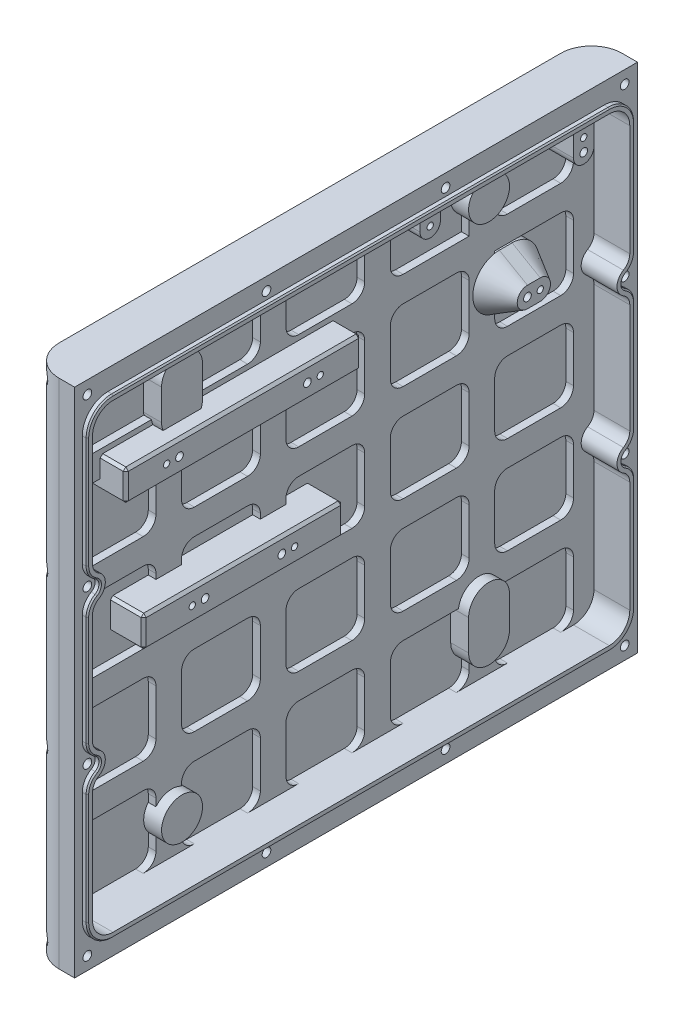
SolidWorks part; units mm, degrees
material "6061 Alloy"
ref_plane "Front Plane" through (0, 0, 0) normal (0, 0, 1) x (1, 0, 0)
ref_plane "Top Plane" through (0, 0, 0) normal (0, 1, 0) x (1, 0, 0)
ref_plane "Right Plane" through (0, 0, 0) normal (1, 0, 0) x (0, 0, -1)
sketch "Sketch1" plane through (0, 0, 0) normal (1, 0, 0) x (0, 0, -1)
  line L0 (-105, 25) -> (-105, -25)
  line L1 (-110, 100) -> (110, 100)
  line L2 (-110, 100) -> (-110, -100)
  line L3 (-110, -100) -> (110, -100)
  line L4 (110, 100) -> (110, -100)
  line L5 (-105, -35) -> (-105, -90)
  line L6 (105, 25) -> (105, -25)
  line L7 (-105, 90) -> (105, 90)
  line L8 (-105, 90) -> (-105, 35)
  line L9 (-105, -90) -> (105, -90)
  line L10 (105, 90) -> (105, 35)
  line L11 (105, -35) -> (105, -90)
  arc A0 (-105, 25) -> (-105, 35) centre (-105, 30) ccw
  arc A1 (-105, -35) -> (-105, -25) centre (-105, -30) ccw
  arc A2 (105, 35) -> (105, 25) centre (105, 30) ccw
  arc A3 (105, -25) -> (105, -35) centre (105, -30) ccw
  point P0 (0, 0)
  point P6 (0, 0)
  dimension "D10" = 60
  dimension "D11" = 10
  dimension "D1" = 220
  dimension "D2" = 200
  dimension "D3" = 210
  dimension "D4" = 180
  dimension "D5" = 90
  dimension "D6" = 100
  dimension "D7" = 105
  dimension "D8" = 110
  dimension "D9" = 60
extrude "Boss-Extrude1" add sketch "Sketch1" along normal blind 6 contours L2 L3 L4 L1
extrude "Boss-Extrude2" add sketch "Sketch1<3>" along normal blind 18
sketch "Sketch1<3>" plane through (0, 0, 0) normal (1, 0, 0) x (0, 0, -1) same geometry as "Sketch1"
sketch "Sketch2" plane through (6, 0, 0) normal (1, 0, 0) x (0, 0, -1)
  line L0 (90, 84) -> (90, 79) construction
  line L1 (94, 90) -> (94, 79)
  line L2 (86, 90) -> (86, 79)
  line L3 (68, 41) -> (73, 41) construction
  line L6 (105, 90) -> (-105, 90) construction
  line L7 (105, 35) -> (105, 90) construction
  line L8 (68, 45) -> (73, 45)
  line L9 (68, 37) -> (73, 37)
  line L10 (26, 84) -> (26, 90)
  line L11 (34, 84) -> (34, 90)
  line L12 (105, 90) -> (-105, 90) construction
  line L13 (34, 90) -> (26, 90)
  line L15 (86, 90) -> (94, 90)
  arc A1 (86, 79) -> (94, 79) centre (90, 79) ccw
  arc A2 (26, 84) -> (34, 84) centre (30, 84) ccw
  arc A5 (68, 45) -> (68, 37) centre (68, 41) ccw
  arc A6 (73, 37) -> (73, 45) centre (73, 41) ccw
  point P2 (90, 81.5)
  point P3 (0, 0)
  point P11 (70.5, 41)
  line M15 (105, 90) -> (-105, 90)
  dimension "D4" = 4
  dimension "D6" = 8
  dimension "D10" = 4
  dimension "D1" = 6
  dimension "D2" = 60
  dimension "D3" = 5
  dimension "D5" = 15
  dimension "D7" = 43
  dimension "D8" = 17
  dimension "D9" = 5
  dimension "D11" = 8
extrude "Boss-Extrude3" add sketch "Sketch2" along normal blind 11 contours L2 A1 L1 M15 | A2 L11 L13 L10 region at (6, 82.901, -90)
extrude "Boss-Extrude7" add sketch "Sketch2<3>" against normal blind 11 draft 30 from offset 11 contours A6 L8 A5 L9 draft outward yes
sketch "Sketch2<3>" plane through (6, 0, 0) normal (1, 0, 0) x (0, 0, -1) same geometry as "Sketch2"
sketch "Sketch3" plane through (17, 0, 0) normal (1, 0, 0) x (0, 0, -1)
  line L0 (94, 79) -> (94, 90) construction
  circle A0 centre (30, 84) radius 1.2295
  circle A1 centre (90, 84) radius 1.2295
  circle A2 centre (73, 41) radius 1.2295
  arc A3 (73, 37) -> (73, 45) centre (73, 41) ccw construction
  point P9 (0, 0)
  point P10 (0, 0)
  dimension "D1" = 2.459
  dimension "D2" = 4
extrude "Cut-Extrude1" cut sketch "Sketch3" against normal blind 7
hole_wizard "Ø3.0mm Dowel Hole1" positions "Sketch4" profile "Sketch5" hole size "Ø3.0" standard "ANSI Metric"
sketch "Sketch4" plane through (17, 0, 0) normal (1, 0, 0) x (0, 0, -1)
  arc A0 (68, 45) -> (68, 37) centre (68, 41) ccw construction
  point P0 (68, 41)
  point P3 (90, 79)
  point P6 (0, 0)
sketch "Sketch5" plane through (17, 41, -68) normal (0, 1, 0) x (0, 0, -1)
  line L0 (0, 0) -> (0, 5.9013)
  line L1 (0, 5.9013) -> (1.5, 5)
  line L2 (1.5, 5) -> (1.5, 0)
  line L5 (1.5, 0) -> (0, 0)
  line L10 (0, 5.9013) -> (-1.5, 5) construction
  line L11 (0, -6.35) -> (0, 107.95) construction
  dimension "Hole Dia." = 3
  dimension "Hole Depth" = 5
  dimension "Drill Angle" = 118
sketch "Sketch6" plane through (6, 0, 0) normal (1, 0, 0) x (0, 0, -1)
  line L0 (-42, 84.1007) -> (-42, -37.9382) construction
  line L1 (-88, 60) -> (4, 60)
  line L2 (-88, 60) -> (-88, 48)
  line L3 (-88, 48) -> (4, 48)
  line L4 (4, 60) -> (4, 48)
  line L5 (-81, 7) -> (-3, 7)
  line L6 (-81, 7) -> (-81, -5)
  line L7 (-81, -5) -> (-3, -5)
  line L8 (-3, 7) -> (-3, -5)
  line L9 (-105, 90) -> (-105, 35) construction
  line L10 (105, 90) -> (94, 90) construction
  dimension "D1" = 63
  dimension "D2" = 12
  dimension "D3" = 12
  dimension "D4" = 30
  dimension "D5" = 41
  dimension "D6" = 78
  dimension "D7" = 92
extrude "Boss-Extrude4" add sketch "Sketch6" along normal blind 10
sketch "Sketch7" plane through (16, 0, 0) normal (1, 0, 0) x (0, 0, -1)
  line L0 (-42, 60) -> (-42, -5) construction
  line L1 (4, 60) -> (-88, 60) construction
  line L2 (-81, -5) -> (-3, -5) construction
  line L3 (-3, 7) -> (-81, 7) construction
  circle A0 centre (-72, 54) radius 1.2295
  circle A1 centre (-12, 54) radius 1.2295
  circle A2 centre (-62, 1) radius 1.2295
  circle A3 centre (-22, 1) radius 1.2295
  dimension "D1" = 30
  dimension "D2" = 2.459
  dimension "D7" = 6
  dimension "D3" = 30
  dimension "D4" = 6
  dimension "D5" = 20
  dimension "D6" = 20
extrude "Cut-Extrude2" cut sketch "Sketch7" against normal blind 7
hole_wizard "Ø3.0mm Dowel Hole2" positions "Sketch9" profile "Sketch10" hole size "Ø3.0" standard "ANSI Metric"
sketch "Sketch9" plane through (16, 0, 0) normal (1, 0, 0) x (0, 0, -1)
  line L0 (4, 60) -> (-88, 60) construction
  line L1 (-3, 7) -> (-81, 7) construction
  circle A0 centre (-72, 54) radius 1.2295 construction
  circle A1 centre (-12, 54) radius 1.2295 construction
  circle A2 centre (-62, 1) radius 1.2295 construction
  circle A3 centre (-22, 1) radius 1.2295 construction
  point P0 (-67, 54)
  point P2 (-17, 54)
  point P4 (-57, 1)
  point P6 (-27, 1)
  dimension "D2" = 5
  dimension "D4" = 5
  dimension "D1" = 6
  dimension "D3" = 5
  dimension "D5" = 5
  dimension "D6" = 6
sketch "Sketch10" plane through (16, 54, 67) normal (0, 1, 0) x (0, 0, -1)
  line L0 (0, 0) -> (0, 4.9013)
  line L1 (0, 4.9013) -> (1.5, 4)
  line L2 (1.5, 4) -> (1.5, 0)
  line L5 (1.5, 0) -> (0, 0)
  line L10 (0, 4.9013) -> (-1.5, 4) construction
  line L11 (0, -6.35) -> (0, 107.95) construction
  dimension "Hole Dia." = 3
  dimension "Hole Depth" = 4
  dimension "Drill Angle" = 118
fillet "Fillet1" radius 8 4 edges at (12, -90, 105) (12, 90, 105) (12, -90, -105) (12, 90, -105)
fillet "Fillet2" radius 5 8 edges at (12, -25, -105) (12, -35, -105) (12, 25, -105) (12, 35, -105) (12, -35, 105) (12, -25, 105) (12, 25, 105) (12, 35, 105)
sketch "Sketch11" plane through (18, 0, 0) normal (1, 0, 0) x (0, 0, -1)
  line L0 (107, -82) -> (107, -38.6603)
  line L1 (-97, -92) -> (97, -92)
  line L2 (-107, -38.6603) -> (-107, -82)
  line L3 (-107, 21.3397) -> (-107, -21.3397)
  line L4 (-107, 82) -> (-107, 38.6603)
  line L5 (97, 92) -> (-97, 92)
  line L6 (107, 38.6603) -> (107, 82)
  line L7 (107, -21.3397) -> (107, 21.3397)
  line L8 (105, -21.3397) -> (105, 21.3397)
  line L9 (105, 38.6603) -> (105, 82)
  line L10 (97, 90) -> (94, 90)
  line L11 (-105, 82) -> (-105, 38.6603)
  line L12 (-105, 21.3397) -> (-105, -21.3397)
  line L13 (-105, -38.6603) -> (-105, -82)
  line L14 (-97, -90) -> (97, -90)
  line L15 (105, -82) -> (105, -38.6603)
  line L16 (105, -21.3397) -> (105, 21.3397)
  line L17 (105, 38.6603) -> (105, 82)
  line L18 (97, 90) -> (94, 90)
  line L19 (-105, 82) -> (-105, 38.6603)
  line L20 (-105, 21.3397) -> (-105, -21.3397)
  line L21 (-105, -38.6603) -> (-105, -82)
  line L22 (-97, -90) -> (97, -90)
  line L23 (105, -82) -> (105, -38.6603)
  line L38 (94, 90) -> (94, 79)
  line L40 (86, 79) -> (86, 90)
  line L42 (86, 90) -> (34, 90)
  line L44 (34, 90) -> (34, 84)
  line L46 (26, 84) -> (26, 90)
  line L48 (26, 90) -> (-97, 90)
  line L49 (94, 90) -> (-97, 90)
  arc A0 (103.5, -27.4019) -> (103.5, -32.5981) centre (105, -30) ccw
  arc A1 (107, -38.6603) -> (103.5, -32.5981) centre (100, -38.6603) ccw
  arc A2 (97, -92) -> (107, -82) centre (97, -82) ccw
  arc A3 (-107, -82) -> (-97, -92) centre (-97, -82) ccw
  arc A4 (-103.5, -32.5981) -> (-107, -38.6603) centre (-100, -38.6603) ccw
  arc A5 (-103.5, -32.5981) -> (-103.5, -27.4019) centre (-105, -30) ccw
  arc A6 (-107, -21.3397) -> (-103.5, -27.4019) centre (-100, -21.3397) ccw
  arc A7 (-103.5, 27.4019) -> (-107, 21.3397) centre (-100, 21.3397) ccw
  arc A8 (-103.5, 27.4019) -> (-103.5, 32.5981) centre (-105, 30) ccw
  arc A9 (-107, 38.6603) -> (-103.5, 32.5981) centre (-100, 38.6603) ccw
  arc A10 (-97, 92) -> (-107, 82) centre (-97, 82) ccw
  arc A11 (107, 82) -> (97, 92) centre (97, 82) ccw
  arc A12 (103.5, 32.5981) -> (107, 38.6603) centre (100, 38.6603) ccw
  arc A13 (103.5, 32.5981) -> (103.5, 27.4019) centre (105, 30) ccw
  arc A14 (107, 21.3397) -> (103.5, 27.4019) centre (100, 21.3397) ccw
  arc A15 (103.5, -27.4019) -> (107, -21.3397) centre (100, -21.3397) ccw
  arc A16 (102.5, -25.6699) -> (102.5, -34.3301) centre (105, -30) ccw
  arc A17 (102.5, -25.6699) -> (105, -21.3397) centre (100, -21.3397) ccw
  arc A18 (105, 21.3397) -> (102.5, 25.6699) centre (100, 21.3397) ccw
  arc A19 (102.5, 34.3301) -> (102.5, 25.6699) centre (105, 30) ccw
  arc A20 (102.5, 34.3301) -> (105, 38.6603) centre (100, 38.6603) ccw
  arc A21 (105, 82) -> (97, 90) centre (97, 82) ccw
  arc A22 (-97, 90) -> (-105, 82) centre (-97, 82) ccw
  arc A23 (-105, 38.6603) -> (-102.5, 34.3301) centre (-100, 38.6603) ccw
  arc A24 (-102.5, 25.6699) -> (-102.5, 34.3301) centre (-105, 30) ccw
  arc A25 (-102.5, 25.6699) -> (-105, 21.3397) centre (-100, 21.3397) ccw
  arc A26 (-105, -21.3397) -> (-102.5, -25.6699) centre (-100, -21.3397) ccw
  arc A27 (-102.5, -34.3301) -> (-102.5, -25.6699) centre (-105, -30) ccw
  arc A28 (-102.5, -34.3301) -> (-105, -38.6603) centre (-100, -38.6603) ccw
  arc A29 (-105, -82) -> (-97, -90) centre (-97, -82) ccw
  arc A30 (97, -90) -> (105, -82) centre (97, -82) ccw
  arc A31 (105, -38.6603) -> (102.5, -34.3301) centre (100, -38.6603) ccw
  arc A32 (102.5, -25.6699) -> (102.5, -34.3301) centre (105, -30) ccw
  arc A33 (102.5, -25.6699) -> (105, -21.3397) centre (100, -21.3397) ccw
  arc A34 (105, 21.3397) -> (102.5, 25.6699) centre (100, 21.3397) ccw
  arc A35 (102.5, 34.3301) -> (102.5, 25.6699) centre (105, 30) ccw
  arc A36 (102.5, 34.3301) -> (105, 38.6603) centre (100, 38.6603) ccw
  arc A37 (105, 82) -> (97, 90) centre (97, 82) ccw
  arc A38 (-97, 90) -> (-105, 82) centre (-97, 82) ccw
  arc A39 (-105, 38.6603) -> (-102.5, 34.3301) centre (-100, 38.6603) ccw
  arc A40 (-102.5, 25.6699) -> (-102.5, 34.3301) centre (-105, 30) ccw
  arc A41 (-102.5, 25.6699) -> (-105, 21.3397) centre (-100, 21.3397) ccw
  arc A42 (-105, -21.3397) -> (-102.5, -25.6699) centre (-100, -21.3397) ccw
  arc A43 (-102.5, -34.3301) -> (-102.5, -25.6699) centre (-105, -30) ccw
  arc A44 (-102.5, -34.3301) -> (-105, -38.6603) centre (-100, -38.6603) ccw
  arc A45 (-105, -82) -> (-97, -90) centre (-97, -82) ccw
  arc A46 (97, -90) -> (105, -82) centre (97, -82) ccw
  arc A47 (105, -38.6603) -> (102.5, -34.3301) centre (100, -38.6603) ccw
  arc A66 (86, 79) -> (94, 79) centre (90, 79) ccw
  arc A68 (26, 84) -> (34, 84) centre (30, 84) ccw
  dimension "D1" = 0
  dimension "D2" = 2
extrude "Boss-Extrude5" add sketch "Sketch11" along normal blind 2
chamfer "Chamfer1" distance 0.5 angle 45 24 edges at (20, -60.3301, -107) (20, -35.1603, -106.0622) (20, -89.0711, -104.0711) (20, -30, -102) (20, -92, 0) (20, -24.8397, -106.0622) (20, -89.0711, 104.0711) (20, 0, -107) (20, -60.3301, 107) (20, 24.8397, -106.0622) (20, -35.1603, 106.0622) (20, 30, -102) (20, -30, 102) (20, 35.1603, -106.0622) (20, -24.8397, 106.0622) (20, 60.3301, -107) (20, 0, 107) (20, 89.0711, -104.0711) (20, 24.8397, 106.0622) (20, 92, 0) (20, 30, 102) (20, 89.0711, 104.0711) (20, 35.1603, 106.0622) (20, 60.3301, 107)
sketch "Sketch12" plane through (18, 0, 0) normal (1, 0, 0) x (0, 0, -1)
  line L0 (110, 100) -> (-110, 100) construction
  line L2 (-110, -100) -> (110, -100) construction
  circle A0 centre (-105, 95) radius 1.7
  circle A1 centre (-105, 30) radius 1.7
  circle A2 centre (-105, -30) radius 1.7
  circle A3 centre (-105, -95) radius 1.7
  circle A4 centre (-35, -95) radius 1.7
  circle A5 centre (35, -95) radius 1.7
  circle A6 centre (105, -95) radius 1.7
  circle A7 centre (105, -30) radius 1.7
  circle A8 centre (105, 30) radius 1.7
  circle A9 centre (105, 95) radius 1.7
  circle A10 centre (-35, 95) radius 1.7
  circle A11 centre (35, 95) radius 1.7
  dimension "D2" = 3.4
  dimension "D3" = 5
  dimension "D1" = 5
  dimension "D4" = 70
  dimension "D5" = 70
extrude "Cut-Extrude3" cut sketch "Sketch12" against normal up to surface (18 mm away) up to face at (0, 0, 0)
sketch "Sketch13" plane through (0, 0, 0) normal (-1, 0, 0) x (0, 0, 1)
  circle A0 centre (-105, 95) radius 3.25
  circle A1 centre (-35, 95) radius 3.25
  circle A2 centre (35, 95) radius 3.25
  circle A3 centre (105, 95) radius 3.25
  circle A4 centre (105, 30) radius 3.25
  circle A5 centre (105, -30) radius 3.25
  circle A6 centre (105, -95) radius 3.25
  circle A7 centre (35, -95) radius 3.25
  circle A8 centre (-35, -95) radius 3.25
  circle A9 centre (-105, -95) radius 3.25
  circle A10 centre (-105, -30) radius 3.25
  circle A11 centre (-105, 30) radius 3.25
  dimension "D1" = 6.5
extrude "Cut-Extrude4" cut sketch "Sketch13" against normal blind 12
fillet "Fillet3" radius 12 2 edges at (0, 0, -110) (0, 0, 110)
sketch "Sketch14" plane through (0, 0, 0) normal (-1, 0, 0) x (0, 0, 1)
  line L0 (60, 75) -> (60, 63) construction
  line L1 (68, 75) -> (68, 63)
  line L2 (52, 75) -> (52, 63)
  line L3 (-60, -75) -> (-60, -63) construction
  line L4 (-68, -75) -> (-68, -63)
  line L5 (-52, -75) -> (-52, -63)
  circle A0 centre (-60, 75) radius 8
  circle A1 centre (60, -75) radius 8
  arc A2 (68, 75) -> (52, 75) centre (60, 75) ccw
  arc A3 (52, 63) -> (68, 63) centre (60, 63) ccw
  arc A4 (-68, -75) -> (-52, -75) centre (-60, -75) ccw
  arc A5 (-52, -63) -> (-68, -63) centre (-60, -63) ccw
  circle A6 centre (-60, -75) radius 2.4585
  circle A7 centre (60, -75) radius 2.4585
  circle A8 centre (-60, 75) radius 2.4585
  circle A9 centre (60, 75) radius 2.4585
  circle A10 centre (60, 63) radius 1.5
  circle A11 centre (-60, -63) radius 1.5
  point P6 (60, 69)
  point P12 (-60, -69)
  dimension "D5" = 16
  dimension "D6" = 8
  dimension "D7" = 12
  dimension "D8" = 4.917
  dimension "D9" = 3
  dimension "D1" = 120
  dimension "D2" = 150
  dimension "D3" = 75
  dimension "D4" = 60
extrude "Boss-Extrude6" add sketch "Sketch14" along normal blind 2 and the other way blind 10 contours A0 | L1 A3 L2 A2 | A1 | L5 A5 L4 A4
extrude "Cut-Extrude6" cut sketch "Sketch14<3>" against normal blind 6 from surface contours A10 | A9 | A8 | A7 | A6 | A11 starting at face at (-2, 69, 60)
sketch "Sketch14<3>" plane through (0, 0, 0) normal (-1, 0, 0) x (0, 0, 1) same geometry as "Sketch14"
sketch "Sketch15" plane through (6, 0, 0) normal (1, 0, 0) x (0, 0, -1)
  line L0 (-97, 90) -> (-97, 62)
  line L1 (97, 90) -> (97, 62)
  line L2 (-66.2, 90) -> (-66.2, 80.0557)
  line L3 (-56.2, 90) -> (-56.2, 82.0399)
  line L4 (-25.4, 90) -> (-25.4, 62)
  line L5 (-15.4, 90) -> (-15.4, 62)
  line L6 (15.4, 90) -> (15.4, 62)
  line L7 (25.4, 90) -> (25.4, 62)
  line L8 (56.2, 90) -> (56.2, 82.0399)
  line L9 (66.2, 90) -> (66.2, 80.0557)
  line L10 (-97, 62) -> (-67.9373, 62)
  line L11 (-97, 52) -> (-88, 52)
  line L12 (-97, 24) -> (-66.2, 24)
  line L13 (-97, 14) -> (-66.2, 14)
  line L14 (105, -21.3397) -> (105, 21.3397)
  line L15 (105, 38.6603) -> (105, 82)
  line L16 (97, 90) -> (94, 90)
  line L17 (94, 90) -> (94, 79)
  line L18 (86, 79) -> (86, 90)
  line L19 (86, 90) -> (34, 90)
  line L20 (34, 90) -> (34, 84)
  line L21 (26, 84) -> (26, 90)
  line L22 (26, 90) -> (-97, 90)
  line L23 (-105, 82) -> (-105, 38.6603)
  line L24 (-105, 21.3397) -> (-105, -21.3397)
  line L25 (-105, -38.6603) -> (-105, -82)
  line L26 (-97, -90) -> (97, -90)
  line L27 (105, -82) -> (105, -38.6603)
  line L30 (97, 90) -> (94, 90)
  line L31 (94, 90) -> (94, 79)
  line L32 (86, 79) -> (86, 90)
  line L33 (86, 90) -> (66.2, 90)
  line L34 (34, 90) -> (34, 84)
  line L35 (26, 84) -> (26, 90)
  line L36 (26, 90) -> (25.4, 90)
  line L40 (-97, -90) -> (-66.2, -90)
  line L42 (-97, -14) -> (-66.2, -14)
  line L43 (-97, -24) -> (-66.2, -24)
  line L44 (-97, -52) -> (-66.2, -52)
  line L45 (-97, -62) -> (-66.2, -62)
  line L46 (-66.2, 90) -> (-97, 90)
  line L47 (-97, -62) -> (-97, -90)
  line L48 (-66.2, -62) -> (-66.2, -69.9443)
  line L49 (-56.2, -62) -> (-56.2, -67.9601)
  line L50 (-56.2, -52) -> (-25.4, -52)
  line L51 (-56.2, -62) -> (-25.4, -62)
  line L52 (-66.2, -80.0557) -> (-66.2, -90)
  line L53 (-56.2, -82.0399) -> (-56.2, -90)
  line L54 (-25.4, -62) -> (-25.4, -90)
  line L55 (-15.4, -62) -> (-15.4, -90)
  line L56 (-15.4, -52) -> (15.4, -52)
  line L57 (-15.4, -62) -> (15.4, -62)
  line L58 (-56.2, -90) -> (-25.4, -90)
  line L59 (-15.4, -90) -> (15.4, -90)
  line L60 (-97, -24) -> (-97, -52)
  line L61 (-66.2, -24) -> (-66.2, -52)
  line L62 (-56.2, -24) -> (-56.2, -52)
  line L63 (-56.2, -14) -> (-25.4, -14)
  line L64 (-56.2, -24) -> (-25.4, -24)
  line L65 (-66.2, -5) -> (-66.2, -14)
  line L66 (-56.2, 14) -> (-56.2, 7)
  line L67 (-66.2, 14) -> (-66.2, 7)
  line L68 (-56.2, 24) -> (-25.4, 24)
  line L69 (-81, 7) -> (-81, -5)
  line L70 (-81, -5) -> (-3, -5)
  line L71 (-3, -5) -> (-3, 7)
  line L72 (-3, 7) -> (-81, 7)
  line L73 (-81, 7) -> (-81, -5)
  line L74 (-81, -5) -> (-66.2, -5)
  line L75 (-3, -5) -> (-3, 7)
  line L76 (-3, 7) -> (-15.4, 7)
  line L77 (-56.2, 14) -> (-25.4, 14)
  line L78 (-97, 14) -> (-97, -14)
  line L79 (-66.2, 7) -> (-81, 7)
  line L80 (-56.2, -5) -> (-25.4, -5)
  line L81 (-56.2, -5) -> (-56.2, -14)
  line L82 (-15.4, 24) -> (15.4, 24)
  line L83 (-15.4, 14) -> (15.4, 14)
  line L84 (-25.4, 14) -> (-25.4, 7)
  line L85 (-15.4, 14) -> (-15.4, 7)
  line L86 (-25.4, 7) -> (-56.2, 7)
  line L87 (-15.4, -5) -> (-3, -5)
  line L88 (-15.4, -14) -> (15.4, -14)
  line L89 (-25.4, -5) -> (-25.4, -14)
  line L90 (-25.4, -24) -> (-25.4, -52)
  line L91 (-15.4, -24) -> (-15.4, -52)
  line L92 (-15.4, -24) -> (15.4, -24)
  line L93 (25.4, -52) -> (56.2, -52)
  line L94 (25.4, -62) -> (52.0627, -62)
  line L95 (4, 48) -> (4, 60) construction
  line L96 (15.4, -62) -> (15.4, -90)
  line L98 (-52, 63) -> (-52, 75) construction
  line L99 (-68, 75) -> (-68, 63) construction
  line L102 (4, 48) -> (4, 52)
  line L105 (-52, 63) -> (-52, 75)
  line L106 (-68, 75) -> (-68, 63)
  line L107 (-97, 52) -> (-97, 24)
  line L108 (-66.2, 48) -> (-66.2, 24)
  line L109 (-56.2, 48) -> (-56.2, 24)
  line L110 (-25.4, 90) -> (-56.2, 90)
  line L111 (4, 52) -> (15.4, 52)
  line L112 (-56.2, 48) -> (-25.4, 48)
  line L113 (-56.2, 48) -> (-25.4, 48)
  line L114 (-88, 60) -> (-88, 48)
  line L115 (-88, 48) -> (4, 48)
  line L116 (4, 48) -> (4, 60)
  line L117 (4, 60) -> (-88, 60)
  line L118 (-88, 52) -> (-88, 48)
  line L119 (-88, 48) -> (-66.2, 48)
  line L120 (4, 48) -> (4, 52)
  line L122 (-97, 52) -> (-88, 52)
  line L123 (-15.4, 48) -> (4, 48)
  line L124 (-15.4, 48) -> (4, 48)
  line L125 (-15.4, 48) -> (-15.4, 24)
  line L126 (-15.4, 62) -> (15.4, 62)
  line L127 (15.4, 52) -> (15.4, 24)
  line L128 (25.4, 52) -> (25.4, 24)
  line L129 (25.4, 62) -> (56.2, 62)
  line L130 (25.4, 52) -> (56.2, 52)
  line L131 (15.4, 90) -> (-15.4, 90)
  line L132 (-25.4, 48) -> (-25.4, 24)
  line L133 (56.2, 90) -> (34, 90)
  line L134 (97, 52) -> (97, 24)
  line L135 (66.2, 62) -> (97, 62)
  line L136 (56.2, 52) -> (56.2, 24)
  line L137 (66.2, 52) -> (66.2, 51.1931)
  line L138 (56.2, 67.9601) -> (56.2, 62)
  line L139 (66.2, 69.9443) -> (66.2, 62)
  line L140 (68, 51.3509) -> (73, 51.3509) construction
  line L141 (68, 51.3509) -> (73, 51.3509)
  line L142 (68, 30.6491) -> (73, 30.6491) construction
  line L143 (68, 30.6491) -> (73, 30.6491)
  line L144 (66.2, 52) -> (97, 52)
  line L145 (66.2, 30.8069) -> (66.2, 24)
  line L146 (66.2, 14) -> (66.2, -14)
  line L147 (56.2, 14) -> (56.2, -14)
  line L148 (66.2, 24) -> (97, 24)
  line L149 (66.2, 14) -> (97, 14)
  line L150 (97, 14) -> (97, -14)
  line L151 (25.4, 24) -> (56.2, 24)
  line L152 (25.4, 14) -> (56.2, 14)
  line L153 (15.4, 14) -> (15.4, -14)
  line L154 (25.4, 14) -> (25.4, -14)
  line L155 (-15.4, -5) -> (-15.4, -14)
  line L156 (25.4, -14) -> (56.2, -14)
  line L157 (25.4, -24) -> (56.2, -24)
  line L158 (15.4, -24) -> (15.4, -52)
  line L159 (25.4, -24) -> (25.4, -52)
  line L160 (66.2, -14) -> (97, -14)
  line L161 (66.2, -24) -> (97, -24)
  line L162 (56.2, -24) -> (56.2, -52)
  line L163 (66.2, -24) -> (66.2, -52)
  line L164 (97, -24) -> (97, -52)
  line L165 (25.4, -62) -> (25.4, -90)
  line L166 (66.2, -80.0557) -> (66.2, -90)
  line L167 (56.2, -82.0399) -> (56.2, -90)
  line L168 (66.2, -52) -> (97, -52)
  line L169 (67.9373, -62) -> (97, -62)
  line L170 (97, -62) -> (97, -90)
  line L171 (66.2, -90) -> (97, -90)
  line L172 (25.4, -90) -> (56.2, -90)
  line L173 (68, -75) -> (68, -63)
  line L174 (52, -63) -> (52, -75)
  line L175 (68, -75) -> (68, -63)
  line L176 (52, -63) -> (52, -75)
  line L177 (-52.0627, 62) -> (-25.4, 62)
  circle A0 centre (-60, -75) radius 8 construction
  arc A1 (-66.2, -69.9443) -> (-66.2, -80.0557) centre (-60, -75) ccw
  arc A2 (-56.2, -82.0399) -> (-56.2, -67.9601) centre (-60, -75) ccw
  arc A3 (-68, 63) -> (-67.4162, 60) centre (-60, 63) ccw construction
  arc A4 (-52.5838, 60) -> (-52, 63) centre (-60, 63) ccw construction
  arc A5 (-52, 75) -> (-68, 75) centre (-60, 75) ccw construction
  arc A6 (-68, 63) -> (-67.9373, 62) centre (-60, 63) ccw
  arc A7 (-52.0627, 62) -> (-52, 63) centre (-60, 63) ccw
  arc A8 (-52, 75) -> (-56.2, 82.0399) centre (-60, 75) ccw
  arc A9 (-66.2, 80.0557) -> (-68, 75) centre (-60, 75) ccw
  circle A10 centre (60, 75) radius 8 construction
  arc A11 (56.2, 82.0399) -> (56.2, 67.9601) centre (60, 75) ccw
  arc A12 (66.2, 69.9443) -> (66.2, 80.0557) centre (60, 75) ccw
  arc A13 (68, 51.3509) -> (68, 30.6491) centre (68, 41) ccw construction
  arc A14 (68, 51.3509) -> (66.2, 51.1931) centre (68, 41) ccw
  arc A15 (73, 30.6491) -> (73, 51.3509) centre (73, 41) ccw construction
  arc A16 (73, 30.6491) -> (73, 51.3509) centre (73, 41) ccw
  arc A17 (66.2, 30.8069) -> (68, 30.6491) centre (68, 41) ccw
  arc A18 (102.5, -25.6699) -> (102.5, -34.3301) centre (105, -30) ccw
  arc A19 (102.5, -25.6699) -> (105, -21.3397) centre (100, -21.3397) ccw
  arc A20 (105, 21.3397) -> (102.5, 25.6699) centre (100, 21.3397) ccw
  arc A21 (102.5, 34.3301) -> (102.5, 25.6699) centre (105, 30) ccw
  arc A22 (102.5, 34.3301) -> (105, 38.6603) centre (100, 38.6603) ccw
  arc A23 (105, 82) -> (97, 90) centre (97, 82) ccw
  arc A24 (86, 79) -> (94, 79) centre (90, 79) ccw
  arc A25 (26, 84) -> (34, 84) centre (30, 84) ccw
  arc A26 (-97, 90) -> (-105, 82) centre (-97, 82) ccw
  arc A27 (-105, 38.6603) -> (-102.5, 34.3301) centre (-100, 38.6603) ccw
  arc A28 (-102.5, 25.6699) -> (-102.5, 34.3301) centre (-105, 30) ccw
  arc A29 (-102.5, 25.6699) -> (-105, 21.3397) centre (-100, 21.3397) ccw
  arc A30 (-105, -21.3397) -> (-102.5, -25.6699) centre (-100, -21.3397) ccw
  arc A31 (-102.5, -34.3301) -> (-102.5, -25.6699) centre (-105, -30) ccw
  arc A32 (-102.5, -34.3301) -> (-105, -38.6603) centre (-100, -38.6603) ccw
  arc A33 (-105, -82) -> (-97, -90) centre (-97, -82) ccw
  arc A34 (97, -90) -> (105, -82) centre (97, -82) ccw
  arc A35 (105, -38.6603) -> (102.5, -34.3301) centre (100, -38.6603) ccw
  arc A42 (86, 79) -> (94, 79) centre (90, 79) ccw
  arc A43 (26, 84) -> (34, 84) centre (30, 84) ccw
  arc A54 (52.0627, -62) -> (52, -63) centre (60, -63) ccw
  arc A55 (66.2, -80.0557) -> (68, -75) centre (60, -75) ccw
  arc A56 (52, -75) -> (68, -75) centre (60, -75) ccw
  arc A57 (68, -63) -> (52, -63) centre (60, -63) ccw
  arc A58 (52, -75) -> (56.2, -82.0399) centre (60, -75) ccw
  arc A59 (68, -63) -> (67.9373, -62) centre (60, -63) ccw
  dimension "D2" = 10
  dimension "D3" = 30.8
  dimension "D5" = 10
  dimension "D6" = 28
  dimension "D1" = 0
  dimension "D8" = 0
  dimension "D9" = 0
  dimension "D10" = 0
  dimension "D4" = 4
  dimension "D7" = 4
extrude "Cut-Extrude5" cut sketch "Sketch15" against normal blind 3 contours A9 L2 L46 L0 L10 A6 L106 | A8 L105 A7 L177 L4 L110 L3 | L132 L112 L109 L68 | L119 L118 L11 L107 L12 L108 | L127 L111 L102 L123 L125 L82 | L6 L131 L5 L126 | A43 L35 L36 L7 L129 L138 A11 L8 L133 L34 | A42 L32 L33 L9 A12 L139 L135 L1 L30 L31 | L128 L151 L136 L130 | A17 L145 L148 L134 L144 L137 A14 L141 A16 L143 | L79 L67 L13 L78 L42 L65 L74 L73 | L89 L80 L81 L63 | L86 L84 L77 L66 | L87 L155 L88 L153 L83 L85 L76 L75 | L154 L156 L147 L152 | L146 L160 L150 L149 | L163 L168 L164 L161 | L162 L157 L159 L93 | L158 L92 L91 L56 | L90 L64 L62 L50 | L61 L43 L60 L44 | A1 L48 L45 L47 L40 L52 | A2 L53 L58 L54 L51 L49 | L96 L57 L55 L59 | A58 L176 A54 L94 L165 L172 L167 | A59 L175 A55 L166 L171 L170 L169 region at (6, 76.2035, 82.1166) region at (6, 76.4729, 39.5114) region at (6, 76, 0) region at (6, 75.1377, -41.0865) region at (6, -76.0146, 81.8147) region at (6, 74.9573, -80.5579) region at (6, -76.0513, 40.0981) region at (6, -76, 0) region at (6, -76.4729, -39.5114) region at (6, -76.2035, -82.1166) region at (6, 36.6502, 82.1062) region at (6, 36.8135, -0.5636) region at (6, 36, 40.8) region at (6, -0.2593, 83.6748) region at (6, 10.5, 40.8) region at (6, -9.5, 40.8) region at (6, -0.2085, -1.9184) region at (6, -38, 81.6) region at (6, -38, 40.8) region at (6, -38, 0) region at (6, -38, -40.8) region at (6, 38, -40.8) region at (6, 36.3259, -85.9258) region at (6, 0, -81.6) region at (6, 0, -40.8) region at (6, -38, -81.6)
fillet "Fillet4" radius 5 40 edges at (4.5, -24, -97) (4.5, -52, -97) (4.5, -52, -66.2) (4.5, -24, -66.2) (4.5, -52, -56.2) (4.5, -24, -56.2) (4.5, -24, -25.4) (4.5, -52, -25.4) (4.5, -52, -15.4) (4.5, -52, 15.4) (4.5, -24, -15.4) (4.5, -24, 15.4) (4.5, -52, 25.4) (4.5, -24, 25.4) (4.5, -52, 56.2) (4.5, -24, 56.2) (4.5, -90, -97) (4.5, -62, -97) (4.5, -90, -66.2) (4.5, -90, -56.2) (4.5, -90, -25.4) (4.5, -62, -25.4) (4.5, -90, -15.4) (4.5, -62, -15.4) (4.5, -62, 15.4) (4.5, -90, 15.4) (4.5, -90, 25.4) (4.5, -90, 56.2) (4.5, -90, 66.2) (4.5, -90, 97) (4.5, -62, 25.4) (4.5, -62, 56.2) (4.5, -62, 66.2) (4.5, -62, 97) (4.5, -52, 66.2) (4.5, -24, 66.2) (4.5, -52, 97) (4.5, -14, 97) (4.5, 14, 97) (4.5, -24, 97)
fillet "Fillet5" radius 5 52 edges at (4.5, -14, 66.2) (4.5, 14, 66.2) (4.5, 62, 97) (4.5, 90, 97) (4.5, 90, 66.2) (4.5, 52, 97) (4.5, 24, 97) (4.5, 48, 66.2) (4.5, 24, 66.2) (4.5, 48, 56.2) (4.5, 48, 15.4) (4.5, 48, 25.4) (4.5, 14, 56.2) (4.5, 14, 25.4) (4.5, -14, 25.4) (4.5, -14, 56.2) (4.5, 14, 15.4) (4.5, -14, 15.4) (4.5, 62, 15.4) (4.5, 62, -15.4) (4.5, 90, 15.4) (4.5, 90, 56.2) (4.5, 90, 25.4) (4.5, 62, 25.4) (4.5, 24, 56.2) (4.5, 24, 25.4) (4.5, 24, -15.4) (4.5, 24, 15.4) (4.5, 52, -15.4) (4.5, 90, -15.4) (4.5, 90, -56.2) (4.5, 90, -66.2) (4.5, 62, -25.4) (4.5, 52, -56.2) (4.5, 52, -25.4) (4.5, 24, -25.4) (4.5, 24, -56.2) (4.5, 62, -66.2) (4.5, 62, -97) (4.5, 52, -97) (4.5, 24, -97) (4.5, 24, -66.2) (4.5, 14, -15.4) (4.5, -14, -15.4) (4.5, -14, -56.2) (4.5, 14, -56.2) (4.5, 14, -25.4) (4.5, -14, -25.4) (4.5, 14, -97) (4.5, 14, -66.2) (4.5, -14, -66.2) (4.5, -14, -97)
chamfer "Chamfer2" distance 1 angle 45 16 edges at (9.5, 7, 3) (9.5, -5, 3) (16, 1, 3) (16, 7, 42) (16, -5, 42) (9.5, -5, 81) (9.5, 7, 81) (16, 1, 81) (9.5, 48, -4) (16, 54, -4) (16, 48, 42) (11, 60, -4) (16, 60, 42) (11, 60, 88) (16, 54, 88) (9.5, 48, 88)
